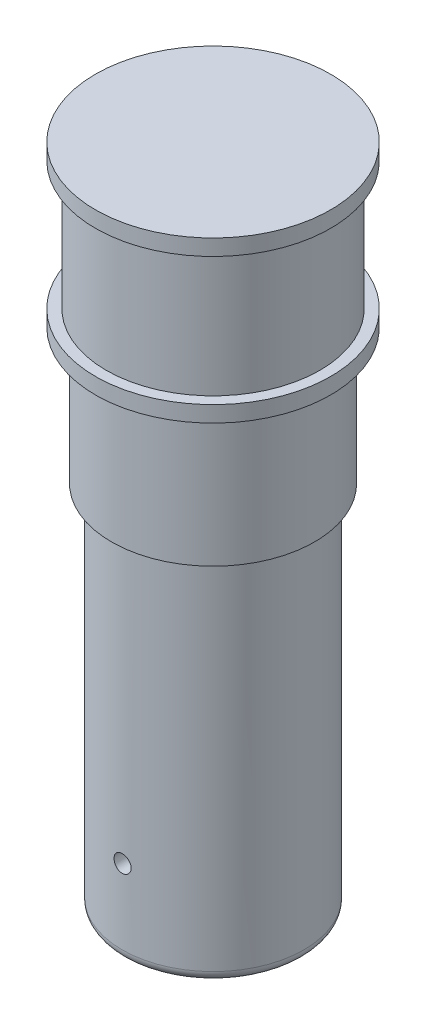
SolidWorks part; units mm, degrees
material "ABS"
ref_plane "Front Plane" through (0, 0, 0) normal (0, 0, 1) x (1, 0, 0)
ref_plane "Top Plane" through (0, 0, 0) normal (0, 1, 0) x (1, 0, 0)
ref_plane "Right Plane" through (0, 0, 0) normal (1, 0, 0) x (0, 0, -1)
sketch "Sketch1" plane through (0, 0, 0) normal (0, 0, 1) x (1, 0, 0)
  line L2 (-8.5, -47.205) -> (-8.5, -12.655)
  line L3 (-9.5, 0) -> (-11, 0)
  line L4 (-11, 0) -> (-11, 1.5)
  line L5 (-11, 1.5) -> (-10, 1.5)
  line L6 (-10, 1.5) -> (-10, 13.5)
  line L7 (-10, 13.5) -> (-11, 13.5)
  line L8 (-11, 13.5) -> (-11, 15)
  line L9 (-11, 15) -> (0, 15)
  line L10 (0, 15) -> (0, -33.205)
  line L11 (-4, -47.205) -> (-8.5, -47.205)
  line L12 (-4, -33.205) -> (-4, -47.205)
  line L13 (0, -33.205) -> (-4, -33.205)
  line L14 (-8.5, -12.655) -> (-9.5, -12.655)
  line L15 (-9.5, -12.655) -> (-9.5, 0)
  dimension "D1" = 8.5
  dimension "D2" = 1
  dimension "D3" = 47.205
  dimension "D4" = 1.5
  dimension "D5" = 4
  dimension "D6" = 14
  dimension "D7" = 15
  dimension "D8" = 10
  dimension "D9" = 34.55
  dimension "D10" = 1
revolve "Revolve1" add sketch "Sketch1" angle 360 about L10
fillet "Fillet1" radius 1 2 edges at (-8.5, -47.205, 0) (-4, -47.205, 0)
hole_wizard "M2x0.4 Tapped Hole1" positions "Sketch2" profile "Sketch3" tap size "M2x0.4" standard "ANSI Metric" end condition up to next
sketch "Sketch2" plane through (0, 0, 0) normal (0, 0, 1) x (1, 0, 0)
  line L0 (-7.5, -47.205) -> (7.5, -47.205) construction
  point P0 (0, -39.205)
  dimension "D1" = 8
sketch "Sketch3" plane through (0, -39.205, 0) normal (1, 0, 0) x (0, 1, 0)
  line L0 (0, 0) -> (0, 8.5)
  line L1 (0, 8.5) -> (0.8, 8.5)
  line L2 (0.8, 8.5) -> (0.8, 0)
  line L5 (0.8, 0) -> (0, 0)
  line L11 (0, -6.35) -> (0, 107.95) construction
  dimension "Thru Tap Drill Dia." = 1.6
  dimension "Thru Tap Drill Depth" = 8.5
cosmetic thread "Hole Thread1" parameters "D2"=2
